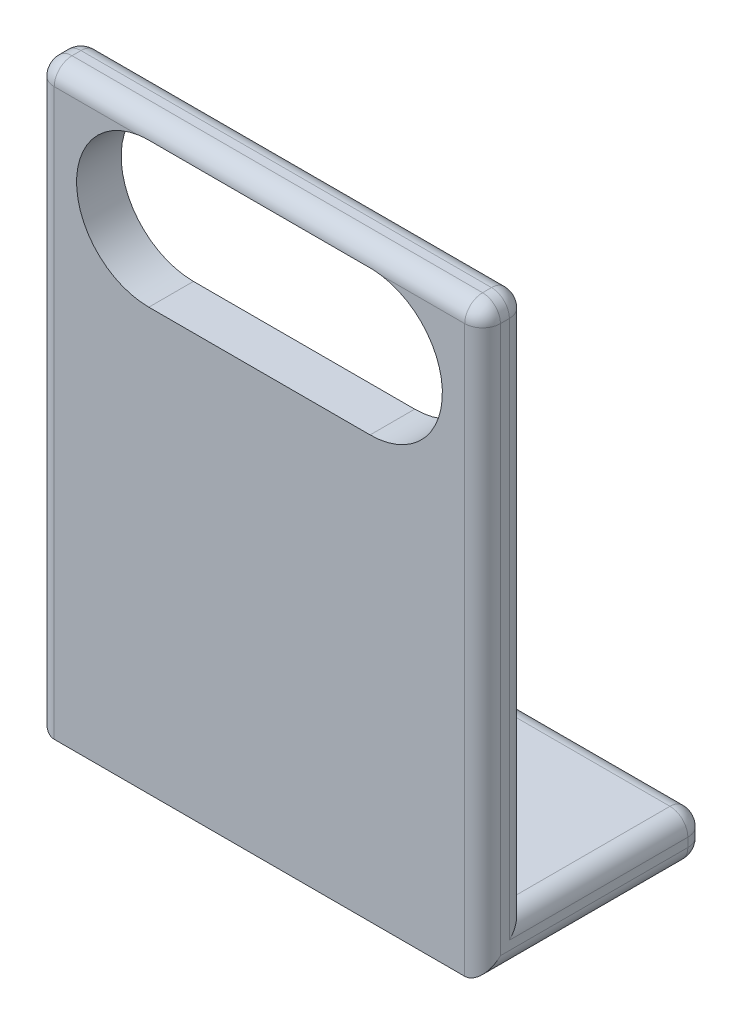
SolidWorks part; units mm, degrees
ref_plane "前视基准面" through (0, 0, 0) normal (0, 0, 1) x (1, 0, 0)
ref_plane "上视基准面" through (0, 0, 0) normal (0, 1, 0) x (1, 0, 0)
ref_plane "右视基准面" through (0, 0, 0) normal (1, 0, 0) x (0, 0, -1)
other "Configuration Table"
sketch "草图2" plane through (0, 0, 0) normal (0, 1, 0) x (1, 0, 0)
  line L1 (0, 0) -> (50, 0)
  line L2 (0, 0) -> (0, 25)
  line L3 (0, 25) -> (50, 25)
  line L4 (50, 0) -> (50, 25)
  dimension "D1" = 50
  dimension "D2" = 25
extrude "凸台-拉伸4" add sketch "草图2" along normal blind 5
sketch "草图7" plane through (0, 5, 0) normal (0, 1, 0) x (1, 0, 0)
  line L0 (50, 0) -> (50, 25) construction
  line L1 (0, 0) -> (50, 0)
  line L2 (0, 0) -> (0, 5)
  line L3 (0, 5) -> (50, 5)
  line L4 (50, 0) -> (50, 5)
  dimension "D1" = 5
extrude "凸台-拉伸5" add sketch "草图7" along normal blind 60.3395
sketch "草图8" plane through (0, 0, -5) normal (0, 0, -1) x (-1, 0, 0)
  line L0 (-50, 65.3395) -> (-50, 55.3395)
  line L1 (-50, 65.3395) -> (-50, 5) construction
  line L7 (-37.3959, 63.4395) -> (-12.6041, 63.4395)
  line L8 (-12.6041, 47.2395) -> (-37.3959, 47.2395)
  arc A3 (-37.3959, 63.4395) -> (-37.3959, 47.2395) centre (-37.3959, 55.3395) ccw
  arc A4 (-12.6041, 63.4395) -> (-12.6041, 47.2395) centre (-12.6041, 55.3395) cw
  point P6 (0, 0)
  point P14 (-37.3959, 55.3395)
  dimension "D1" = 10
extrude "切除-拉伸2" cut sketch "草图8" against normal blind 10 contours A4 L8 A3 L7
fillet "圆角1" radius 2 1 edges at (25, 65.3395, -5)
fillet "圆角2" radius 2 1 edges at (25, 65.3395, 0)
fillet "圆角3" radius 2 8 edges at (0, 0, -12.5) (0, 2.5, -25) (0, 5, -15) (0, 34.1698, -5) (0, 64.7537, -4.4142) (0, 65.3395, -2.5) (0, 64.7537, -0.5858) (0, 31.6698, 0)
fillet "圆角4" radius 2 8 edges at (50, 64.7537, -4.4142) (50, 34.1698, -5) (50, 5, -15) (50, 2.5, -25) (50, 0, -12.5) (50, 31.6698, 0) (50, 64.7537, -0.5858) (50, 65.3395, -2.5)
fillet "圆角5" radius 2 6 edges at (49.4142, 0.5858, -24.4142) (0.5858, 0.5858, -24.4142) (49.4142, 4.4142, -24.4142) (0.5858, 4.4142, -24.4142) (25, 0, -25) (25, 5, -25)
equation "\"25、2\"=11.1014"
